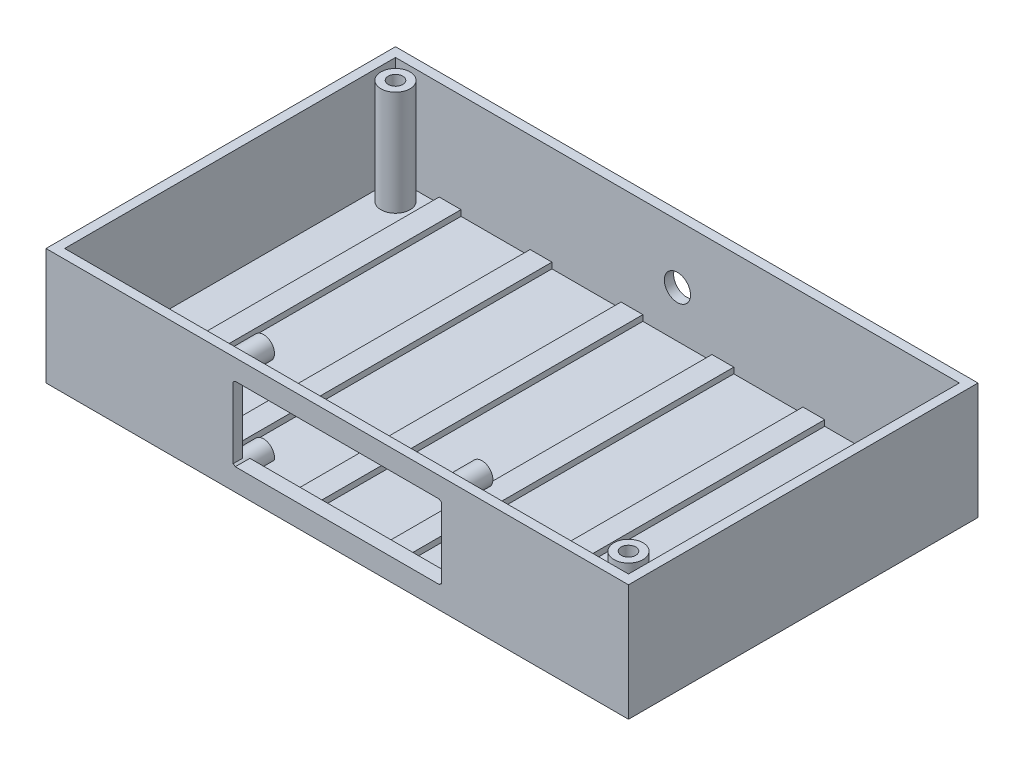
SolidWorks part; units mm, degrees
ref_plane "Alzado" through (0, 0, 0) normal (0, 0, 1) x (1, 0, 0)
ref_plane "Planta" through (0, 0, 0) normal (0, 1, 0) x (1, 0, 0)
ref_plane "Vista lateral" through (0, 0, 0) normal (1, 0, 0) x (0, 0, -1)
sketch "Croquis1" plane through (0, 0, 0) normal (0, 1, 0) x (1, 0, 0)
  line L1 (-100, 60) -> (100, 60)
  line L2 (-100, 60) -> (-100, -60)
  line L3 (-100, -60) -> (100, -60)
  line L4 (100, 60) -> (100, -60)
  line L5 (-100, 60) -> (100, -60) construction
  line L6 (-100, -60) -> (100, 60) construction
  point P0 (0, 0)
  dimension "D1" = 120
  dimension "D2" = 200
extrude "Saliente-Extruir1" add sketch "Croquis1" along normal blind 40
sketch "Croquis2" plane through (0, 40, 0) normal (0, 1, 0) x (1, 0, 0)
  line L1 (-96.8, 56.8) -> (96.8, 56.8)
  line L2 (-96.8, 56.8) -> (-96.8, -56.8)
  line L3 (-96.8, -56.8) -> (96.8, -56.8)
  line L4 (96.8, 56.8) -> (96.8, -56.8)
  line L5 (-96.8, 56.8) -> (96.8, -56.8) construction
  line L6 (-96.8, -56.8) -> (96.8, 56.8) construction
  point P0 (0, 0)
  dimension "D1" = 113.6
  dimension "D2" = 193.6
extrude "Cortar-Extruir1" cut sketch "Croquis2" against normal blind 36
sketch "Croquis3" plane through (0, 0, 60) normal (0, 0, 1) x (1, 0, 0)
  line L0 (-35.75, 40) -> (-35.75, 0) construction
  line L1 (-100, 40) -> (100, 40) construction
  line L2 (-100, 0) -> (100, 0) construction
  line L3 (35.75, 50) -> (35.75, 0) construction
  line L4 (-100, 40) -> (-100, 0) construction
  line L5 (100, 40) -> (100, 0) construction
  line L7 (-35.75, 33) -> (35.75, 33)
  line L8 (-35.75, 33) -> (-35.75, 7.6)
  line L9 (-35.75, 7.6) -> (35.75, 7.6)
  line L10 (35.75, 33) -> (35.75, 7.6)
  dimension "D1" = 64.25
  dimension "D2" = 64.25
  dimension "D3" = 25.4
  dimension "D4" = 7
extrude "Cortar-Extruir2" cut sketch "Croquis3" against normal blind 3.5
sketch "Croquis4" plane through (0, 0, 60) normal (0, 0, 1) x (1, 0, 0)
  line L1 (-37.5, 35.8) -> (37.5, 35.8) construction
  line L2 (-37.5, 35.8) -> (-37.5, 4.8) construction
  line L3 (-37.5, 4.8) -> (37.5, 4.8) construction
  line L4 (37.5, 35.8) -> (37.5, 4.8) construction
  line L5 (-37.5, 35.8) -> (37.5, 4.8) construction
  line L6 (-37.5, 4.8) -> (37.5, 35.8) construction
  line L8 (35.75, 7.6) -> (35.75, 33) construction
  line L9 (-35.75, 7.6) -> (35.75, 7.6) construction
  circle A0 centre (-37.5, 35.8) radius 3.75
  circle A1 centre (37.5, 35.8) radius 3.75
  circle A2 centre (37.5, 4.8) radius 3.75
  circle A3 centre (-37.5, 4.8) radius 3.75
  point P0 (0, 20.3)
  dimension "D5" = 7.5
  dimension "D1" = 31
  dimension "D2" = 2.8
  dimension "D3" = 1.75
  dimension "D4" = 75
extrude "Saliente-Extruir2" add sketch "Croquis4" against normal blind 12.2
sketch "Croquis5" plane through (0, 0, 60) normal (0, 0, 1) x (1, 0, 0)
  line L0 (-35.0055, 7.6) -> (35.0055, 7.6) construction
  line L1 (-35.75, 7.6) -> (35.75, 7.6)
  line L2 (-35.75, 7.6) -> (-35.75, 3.6)
  line L3 (-35.75, 3.6) -> (35.75, 3.6)
  line L4 (35.75, 7.6) -> (35.75, 3.6)
  line L5 (35.0055, 33) -> (-35.0055, 33) construction
  line L6 (-35.75, 33) -> (35.75, 33)
  line L7 (-35.75, 33) -> (-35.75, 37)
  line L8 (-35.75, 37) -> (35.75, 37)
  line L9 (35.75, 33) -> (35.75, 37)
  line L12 (35.75, 8.1166) -> (35.75, 32.4834) construction
  point P12 (35.75, 35)
  dimension "D1" = 4
  dimension "D2" = 4
  dimension "D3" = 71.5
  dimension "D4" = 71.5
  dimension "D5" = 0
  dimension "D6" = 0
extrude "Saliente-Extruir3" add sketch "Croquis5" against normal blind 5
sketch "Croquis6" plane through (0, 4, 0) normal (0, 1, 0) x (1, 0, 0)
  line L0 (96.8, 56.8) -> (-96.8, 56.8) construction
  line L1 (-81.8, 56.8) -> (-74.3, 56.8)
  line L2 (-81.8, 56.8) -> (-81.8, -56.8)
  line L3 (-81.8, -56.8) -> (-74.3, -56.8)
  line L4 (-74.3, 56.8) -> (-74.3, -56.8)
  line L5 (-96.8, -56.8) -> (-41.1637, -56.8) construction
  line L6 (-96.8, 56.8) -> (-96.8, -56.8) construction
  line L7 (-50.58, 56.8) -> (-50.58, -56.8)
  line L8 (-50.58, 56.8) -> (-43.08, 56.8)
  line L9 (-43.08, 56.8) -> (-43.08, -56.8)
  line L10 (-50.58, -56.8) -> (-43.08, -56.8)
  line L11 (-19.36, 56.8) -> (-19.36, -56.8)
  line L12 (-19.36, 56.8) -> (-11.86, 56.8)
  line L13 (-11.86, 56.8) -> (-11.86, -56.8)
  line L14 (-19.36, -56.8) -> (-11.86, -56.8)
  line L15 (11.86, 56.8) -> (11.86, -56.8)
  line L16 (11.86, 56.8) -> (19.36, 56.8)
  line L17 (19.36, 56.8) -> (19.36, -56.8)
  line L18 (11.86, -56.8) -> (19.36, -56.8)
  line L19 (43.08, 56.8) -> (43.08, -56.8)
  line L20 (43.08, 56.8) -> (50.58, 56.8)
  line L21 (50.58, 56.8) -> (50.58, -56.8)
  line L22 (43.08, -56.8) -> (50.58, -56.8)
  line L23 (74.3, 56.8) -> (74.3, -56.8)
  line L24 (74.3, 56.8) -> (81.8, 56.8)
  line L25 (81.8, 56.8) -> (81.8, -56.8)
  line L26 (74.3, -56.8) -> (81.8, -56.8)
  line L27 (96.8, -56.8) -> (96.8, 56.8) construction
  line L28 (-100, 60) -> (-100, -60) construction
  line L29 (100, 60) -> (-100, 60) construction
  line L30 (100, -60) -> (100, 60) construction
  line L31 (-100, -60) -> (100, -60) construction
  circle A0 centre (-90, 50) radius 5
  circle A1 centre (90, 50) radius 5
  circle A2 centre (90, -50) radius 5
  circle A3 centre (-90, -50) radius 5
  dimension "D5" = 10
  dimension "D1" = 7.5
  dimension "D2" = 15
  dimension "D4" = 15
  dimension "D6" = 10
  dimension "D7" = 10
  dimension "D8" = 10
  dimension "D9" = 10
  dimension "D10" = 10
  dimension "D11" = 10
  dimension "D12" = 10
  dimension "D13" = 10
  dimension "D3" = 6
extrude "Saliente-Extruir4" add sketch "Croquis6" along normal blind 2 and the other way blind 5 contours L2 L1 L4 L3 | L7 L10 L9 L8 | L11 L14 L13 L12 | L15 L18 L17 L16 | L19 L22 L21 L20 | L23 L26 L25 L24
sketch "Croquis7" plane through (0, 0, -60) normal (0, 0, -1) x (-1, 0, 0)
  line L0 (0, 40) -> (0, 0) construction
  line L1 (-100, 40) -> (100, 40) construction
  line L2 (-100, 0) -> (100, 0) construction
  circle A0 centre (0, 20) radius 4.5
  dimension "D2" = 9
  dimension "D1" = 0
  dimension "D3" = 20
extrude "Cortar-Extruir3" cut sketch "Croquis7" against normal blind 3.3
extrude "Saliente-Extruir5" add sketch "Croquis6<5>" along normal blind 36 contours A0 | A2 region at (-90, 4, -50) region at (90, 4, 50)
sketch "Croquis6<5>" plane through (0, 4, 0) normal (0, 1, 0) x (1, 0, 0) same geometry as "Croquis6"
extrude "Saliente-Extruir6" add sketch "Croquis6<6>" along normal blind 5 and the other way blind 5 contours A1 | A3 region at (90, 4, -50)
sketch "Croquis6<6>" plane through (0, 4, 0) normal (0, 1, 0) x (1, 0, 0) same geometry as "Croquis6"
sketch "Croquis8" plane through (0, 40, 0) normal (0, 1, 0) x (1, 0, 0)
  circle A0 centre (-90, 50) radius 2.5
  circle A1 centre (90, -50) radius 2.5
  dimension "D1" = 5
  dimension "D2" = 5
extrude "Cortar-Extruir4" cut sketch "Croquis8" against normal blind 20
sketch "Croquis9" plane through (0, 9, 0) normal (0, 1, 0) x (1, 0, 0)
  circle A0 centre (-90, -50) radius 2.5
  circle A1 centre (90, 50) radius 2.5
  dimension "D1" = 5
  dimension "D2" = 5
extrude "Cortar-Extruir5" cut sketch "Croquis9" against normal through all
